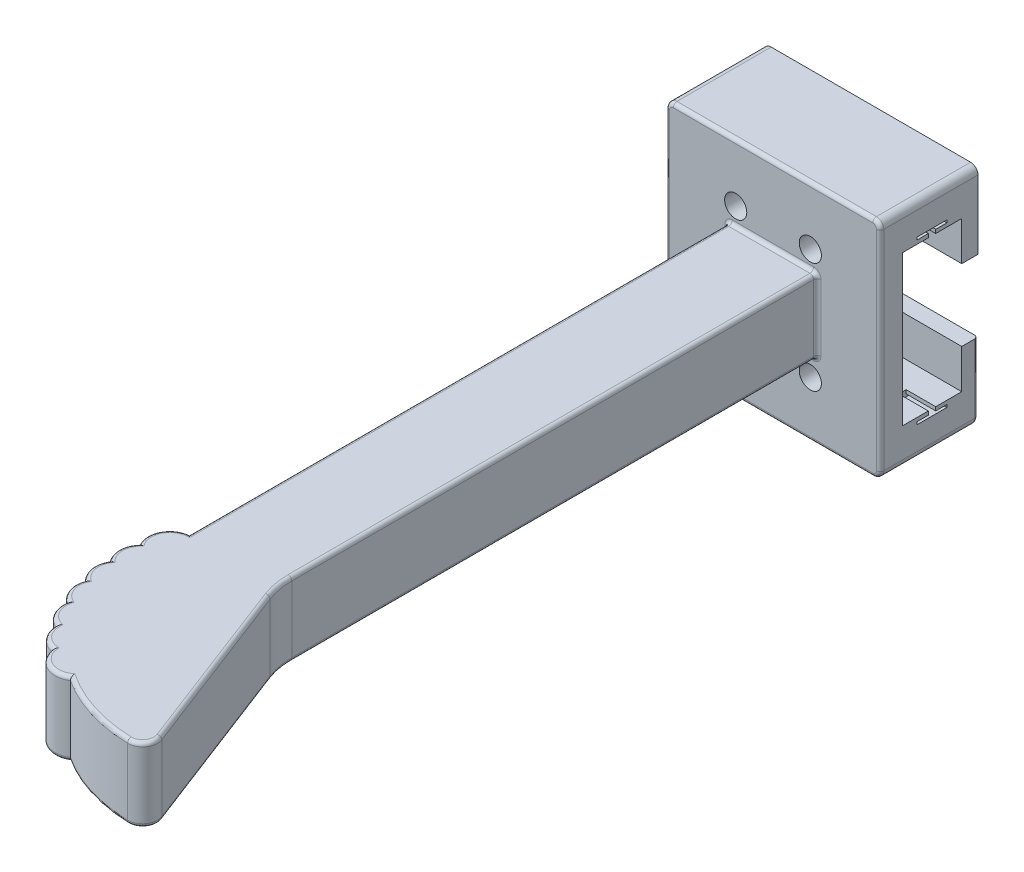
SolidWorks part; units mm, degrees
ref_plane "Plan de face" through (0, 0, 0) normal (0, 0, 1) x (1, 0, 0)
ref_plane "Plan de dessus" through (0, 0, 0) normal (0, 1, 0) x (1, 0, 0)
ref_plane "Plan de droite" through (0, 0, 0) normal (1, 0, 0) x (0, 0, -1)
sketch "Esquisse1" plane through (0, 0, 0) normal (0, 0, 1) x (1, 0, 0)
  line L2 (-14.5, 10.15) -> (14.5, 10.15)
  line L4 (-25.5134, 0) -> (42.2123, 0) construction
  line L5 (0, -19.3923) -> (0, 34.0598) construction
  line L6 (-14.5, -10.15) -> (14.5, -10.15)
  line L7 (-13.5, 15.15) -> (13.5, 15.15)
  line L8 (-14.5, 10.15) -> (-14.5, 14.15)
  line L9 (14.5, 10.15) -> (14.5, 14.15)
  line L10 (-14.5, 15.15) -> (14.5, 15.15) construction
  line L11 (14.5, -10.15) -> (14.5, -14.15)
  line L12 (-13.5, -15.15) -> (13.5, -15.15)
  line L13 (-14.5, -10.15) -> (-14.5, -14.15)
  arc A0 (13.5, 15.15) -> (14.5, 14.15) centre (13.5, 14.15) cw
  arc A1 (-13.5, 15.15) -> (-14.5, 14.15) centre (-13.5, 14.15) ccw
  arc A2 (13.5, -15.15) -> (14.5, -14.15) centre (13.5, -14.15) ccw
  arc A3 (-13.5, -15.15) -> (-14.5, -14.15) centre (-13.5, -14.15) cw
  point P9 (0, 10.15)
  point P13 (0, 0)
  dimension "D4" = 1
  dimension "D1" = 29
  dimension "D2" = 10.15
  dimension "D3" = 5
extrude "Boss.-Extru.1" add sketch "Esquisse1" along normal blind 13.25
sketch "Esquisse2" plane through (0, 10.15, 0) normal (0, -1, 0) x (1, 0, 0)
  line L0 (-14.5, 10.25) -> (14.5, 10.25)
  line L4 (-14.5, 0) -> (14.5, 0)
  line L5 (14.5, 0) -> (14.5, 13.25)
  line L6 (14.5, 13.25) -> (-14.5, 13.25)
  line L7 (-14.5, 13.25) -> (-14.5, 0)
  line L8 (-14.5, 0) -> (14.5, 0)
  line L9 (14.5, 0) -> (14.5, 13.25)
  line L10 (14.5, 13.25) -> (-14.5, 13.25)
  line L11 (-14.5, 13.25) -> (-14.5, 10.25)
  line M7 (14.5, 0) -> (14.5, 13.25)
  line M8 (14.5, 13.25) -> (-14.5, 13.25)
  line M9 (-14.5, 13.25) -> (-14.5, 0)
  dimension "D2" = 3
  dimension "D1" = 0
extrude "Boss.-Extru.2" add sketch "Esquisse2" along normal up to surface (20.3 mm away) contours L0 M9 M7 M8 up to face at (0, -10.15, 6.625)
sketch "Esquisse3" plane through (0, -10.15, 0) normal (0, 1, 0) x (1, 0, 0)
  line L0 (-14.5, -2.2) -> (14.5, -2.2)
  line L4 (-14.5, 0) -> (-14.5, -10.25)
  line L5 (-14.5, -10.25) -> (14.5, -10.25)
  line L6 (14.5, -10.25) -> (14.5, 0)
  line L7 (14.5, 0) -> (-14.5, 0)
  line L8 (-14.5, 0) -> (-14.5, -10.25)
  line L9 (-14.5, -10.25) -> (14.5, -10.25)
  line L10 (14.5, -10.25) -> (14.5, 0)
  line L11 (14.5, 0) -> (-14.5, 0)
  line M6 (-14.5, 0) -> (-14.5, -10.25)
  line M8 (14.5, -10.25) -> (14.5, 0)
  line M9 (14.5, 0) -> (-14.5, 0)
  dimension "D2" = 2.2
  dimension "D1" = 0
extrude "Boss.-Extru.3" add sketch "Esquisse3" along normal blind 5.3 contours L0 M6 M8 M9
mirror "Symétrie1" about plane through (0, 0, 0) normal (0, 1, 0) of "Boss.-Extru.3"
sketch "Esquisse4" plane through (-14.5, 0, 0) normal (-1, 0, 0) x (0, 0, 1)
  line L0 (6.225, -7.9373) -> (6.225, -16.0212) construction
  line L1 (4.225, -10.9998) -> (4.225, -10.65)
  line L2 (10.25, -10.15) -> (2.2, -10.15) construction
  line L3 (8.225, -10.9998) -> (8.225, -10.65)
  line L5 (4.225, -10.65) -> (5.725, -10.65)
  line L6 (4.225, -10.9998) -> (8.225, -10.9998)
  line L7 (5.725, -10.65) -> (5.725, -10.15)
  line L8 (6.725, -10.65) -> (6.725, -10.15)
  line L9 (5.725, -10.15) -> (6.725, -10.15)
  line L10 (6.725, -10.65) -> (8.225, -10.65)
  line L12 (0, -4.85) -> (0, -14.15)
  line L13 (0, -14.15) -> (13.25, -14.15)
  line L14 (13.25, -14.15) -> (13.25, 14.15)
  line L15 (13.25, 14.15) -> (0, 14.15)
  line L16 (0, 14.15) -> (0, 4.85)
  line L17 (0, 4.85) -> (2.2, 4.85)
  line L18 (2.2, 4.85) -> (2.2, 10.15)
  line L19 (2.2, 10.15) -> (10.25, 10.15)
  line L20 (10.25, 10.15) -> (10.25, -10.15)
  line L21 (10.25, -10.15) -> (2.2, -10.15)
  line L22 (2.2, -10.15) -> (2.2, -4.85)
  line L23 (2.2, -4.85) -> (0, -4.85)
  line L24 (0, -4.85) -> (0, -14.15)
  line L25 (6.225, -14.15) -> (13.25, -14.15)
  line L26 (13.25, -14.15) -> (13.25, 14.15)
  line L27 (13.25, 14.15) -> (0, 14.15)
  line L28 (0, 14.15) -> (0, 4.85)
  line L29 (0, 4.85) -> (2.2, 4.85)
  line L30 (2.2, 4.85) -> (2.2, 10.15)
  line L31 (2.2, 10.15) -> (10.25, 10.15)
  line L32 (10.25, 10.15) -> (10.25, -10.15)
  line L34 (2.2, -10.15) -> (2.2, -4.85)
  line L35 (2.2, -4.85) -> (0, -4.85)
  dimension "D2" = 0.5
  dimension "D3" = 2
  dimension "D4" = 0.5
  dimension "D1" = 0
extrude "Enlèv. mat.-Extru.2" cut sketch "Esquisse4" against normal blind 4 contours L0 L5 L1 L6 | L5 L0 L6 L3
mirror "Symétrie2" about plane through (0, 0, 0) normal (0, 1, 0) of "Enlèv. mat.-Extru.2"
mirror "Symétrie3" about plane through (0, 0, 0) normal (1, 0, 0) of "Enlèv. mat.-Extru.2", "Symétrie2"
sketch "Esquisse5" plane through (0, 0, 13.25) normal (0, 0, 1) x (1, 0, 0)
  line L0 (0, 29.1921) -> (0, -27.9353) construction
  circle A0 centre (5.05, 7.35) radius 1.5
  circle A1 centre (5.05, -7.65) radius 1.5
  circle A2 centre (-5.05, -7.65) radius 1.5
  circle A3 centre (-5.05, 7.35) radius 1.5
  dimension "D1" = 3
  dimension "D2" = 3
extrude "Enlèv. mat.-Extru.3" cut sketch "Esquisse5" against normal blind 10
ref_plane "Plan1" through (0, 0, 0) normal (0, -1, 0) x (-1, 0, 0)
sketch "Esquisse6" plane through (0, 0, 0) normal (0, -1, 0) x (-1, 0, 0)
  line L0 (13.5, -13.25) -> (-13.5, -13.25) construction
  line L1 (6, -13.25) -> (-6, -13.25)
  line L2 (0, 15.0109) -> (0, -51.7099) construction
  line L3 (6, -13.25) -> (6, -86.25)
  line L4 (-6, -13.25) -> (-6, -84.3946)
  line L5 (-15.8249, -111.8151) -> (-6.6656, -87.9819)
  arc A0 (6, -86.25) -> (-13.91, -114.532) centre (-14.4271, -93.0189) cw
  arc A1 (-6, -84.3946) -> (-6.6656, -87.9819) centre (-16, -84.3946) cw
  arc A2 (-13.91, -114.532) -> (-15.8249, -111.8151) centre (-13.958, -112.5326) cw
  point P13 (-6, -86.25)
  dimension "D2" = 10
  dimension "D3" = 2
  dimension "D1" = 6
  dimension "D4" = 73
extrude "Boss.-Extru.4" add sketch "Esquisse6" along normal blind 5 and the other way blind 5
sketch "Esquisse7" plane through (0, -5, 0) normal (0, -1, 0) x (1, 0, 0)
  arc A0 (13.91, 114.532) -> (-6, 86.25) centre (14.4271, 93.0189) ccw construction
  arc A1 (13.91, 114.532) -> (-6, 86.25) centre (14.4271, 93.0189) ccw
  arc A2 (-6, 86.25) -> (-7.0624, 91.8855) centre (-5.6644, 89.2312) cw
  dimension "D1" = 3
extrude "Boss.-Extru.5" add sketch "Esquisse7" against normal up to surface (10 mm away) contours A2 A1 up to face at (4.2624, 5, 73.8616)
pattern_circular "Répétition circulaire1" count 7 every 10 about axis through (14.4271, 0, 93.0189) along (0, 1, 0) of "Boss.-Extru.5"
sketch "Esquisse10" plane through (0, 0, 0) normal (0, 0, -1) x (-1, 0, 0)
  line L0 (-22.1706, 0) -> (25.0407, 0) construction
  line L4 (14.5, 10.15) -> (-14.5, 10.15)
  line L5 (14.5, 4.85) -> (14.5, 10.15)
  line L6 (-14.5, 4.85) -> (14.5, 4.85)
  line L7 (-14.5, 10.15) -> (-14.5, 4.85)
  line L9 (14.5, 4.85) -> (14.5, 10.15)
  line L11 (-14.5, 10.15) -> (-14.5, 4.85)
  circle A0 centre (0, 7.5) radius 1.5
  circle A1 centre (0, -7.5) radius 1.5
  dimension "D2" = 3
  dimension "D3" = 14.5
  dimension "D1" = 0
extrude "Enlèv. mat.-Extru.4" cut sketch "Esquisse10" against normal up to surface (2.2 mm away) contours A0 | A1 up to face at (0, -7.5, 2.2)
fillet "Congé2" radius 0.5 30 edges at (-6, 0, 13.25) (-6, 5, 49.75) (8.0643, 5, 113.5761) (15.5928, 5, 113.6848) (11.2453, 5, 99.8985) (6.1678, 5, 86.2189) (6, 5, 48.8223) (6, 0, 13.25) (0, 5, 13.25) (-6, -5, 49.75) (0, -5, 13.25) (6, -5, 48.8223) (6.1678, -5, 86.2189) (11.2453, -5, 99.8985) (15.5928, -5, 113.6848) (8.0643, -5, 113.5761) (-8.3513, -5, 87.897) (-8.3513, 5, 87.897) (-9.0166, -5, 92.7421) (-9.0166, 5, 92.7421) (-8.7085, 5, 96.8173) (-7.6975, 5, 100.777) (-6.0142, 5, 104.5011) (-3.7097, 5, 107.8762) (-0.1642, 5, 111.2448) (-8.7085, -5, 96.8173) (-7.6975, -5, 100.777) (-6.0142, -5, 104.5011) (-3.7097, -5, 107.8762) (-0.1642, -5, 111.2448)
fillet "Congé3" radius 0.5 13 edges at (-14.2071, -14.8571, 13.25) (-14.5, 0, 13.25) (-14.2071, 14.8571, 13.25) (0, 15.15, 13.25) (14.2071, 14.8571, 13.25) (14.5, 0, 13.25) (14.2071, -14.8571, 13.25) (-14.5, -9.5, 0) (-14.2071, -14.8571, 0) (14.5, -9.5, 0) (14.2071, -14.8571, 0) (0, -15.15, 13.25) (0, -15.15, 0)
